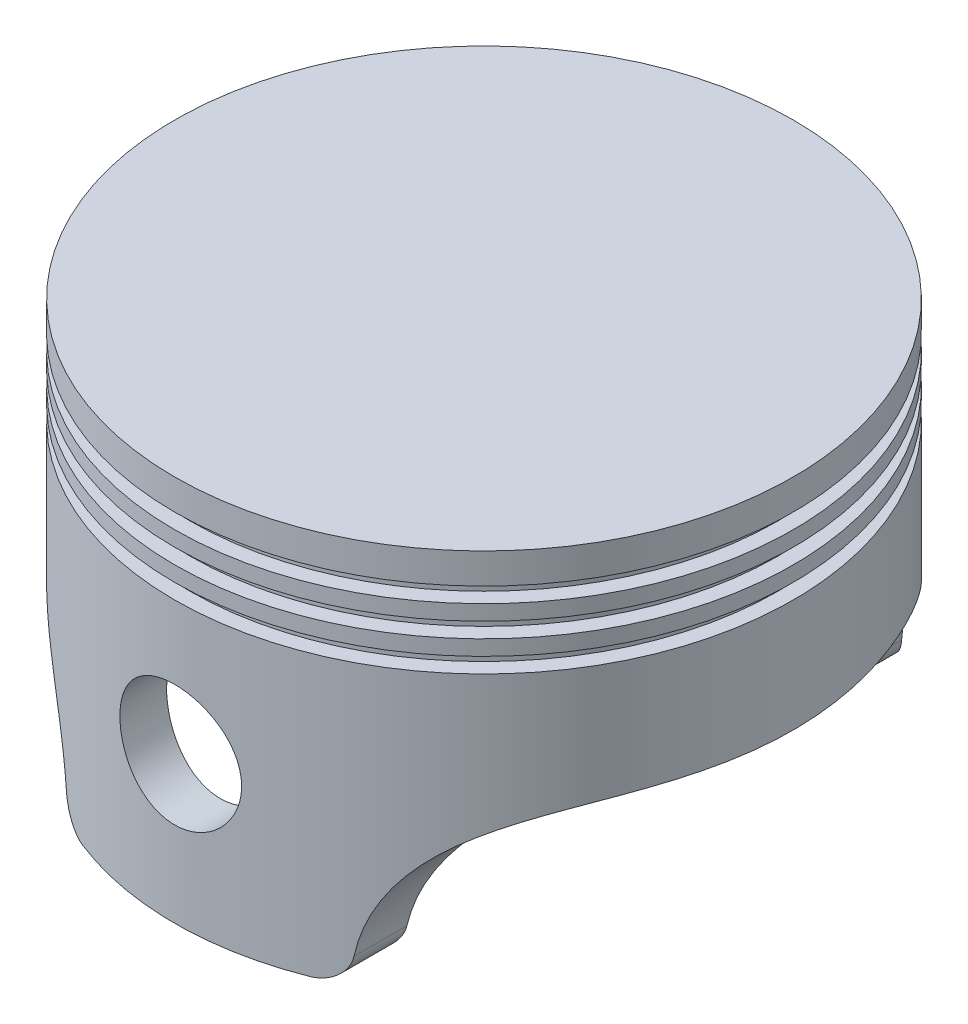
SolidWorks part; units mm, degrees
material "Plain Carbon Steel"
ref_plane "Front Plane" through (0, 0, 0) normal (0, 0, 1) x (1, 0, 0)
ref_plane "Top Plane" through (0, 0, 0) normal (0, 1, 0) x (1, 0, 0)
ref_plane "Right Plane" through (0, 0, 0) normal (1, 0, 0) x (0, 0, -1)
sketch "Sketch2" plane through (0, 0, 0) normal (0, 1, 0) x (1, 0, 0)
  circle A0 centre (0, 0) radius 50.8
  dimension "D1" = 101.6
extrude "Boss-Extrude1" add sketch "Sketch2" along normal mid plane 63.5
shell "Shell1" thickness 7.5 removed face at (0, -31.75, 50.8)
sketch "Sketch4" plane through (0, 24.25, 0) normal (0, -1, 0) x (1, 0, 0)
  line L0 (-42.6455, 7.5) -> (42.6455, 7.5)
  line L2 (-41.4565, 12.5) -> (41.4565, 12.5)
  circle A2 centre (0, 0) radius 43.3 construction
  arc A4 (-42.6455, 7.5) -> (-41.4565, 12.5) centre (0, 0) cw
  arc A5 (41.4565, 12.5) -> (42.6455, 7.5) centre (0, 0) cw
  circle A6 centre (0, 0) radius 43.3 construction
  dimension "D1" = 5
  dimension "D2" = 7.5
extrude "Boss-Extrude5" add sketch "Sketch4" along normal blind 28.5 contours A5 L0 A4 L2
mirror "Mirror1" about plane through (0, 0, 0) normal (0, 0, 1) of "Boss-Extrude5"
sketch "Sketch6" plane through (0, 0, 0) normal (0, 0, 1) x (1, 0, 0)
  line L0 (0, 0) -> (0, 58.5754) construction
  line L15 (-50.8, -31.75) -> (50.8, -31.75) construction
  line L16 (0, -7.75) -> (0, -31.75) construction
  line L17 (50.8, -31.75) -> (50.8, -4.25)
  line L18 (50.8, -31.75) -> (50.8, 31.75) construction
  line L20 (50.8, -31.75) -> (23.3, -31.75)
  circle A1 centre (0, -7.75) radius 10
  arc A2 (23.3, -31.75) -> (50.8, -4.25) centre (50.8, -31.75) cw
  dimension "D7" = 24
  dimension "D6" = 20
  dimension "D8" = 27.5
extrude "Cut-Extrude2" cut sketch "Sketch6" against normal through all both and the other way through all
mirror "Mirror2" about plane through (0, 0, 0) normal (1, 0, 0) of "Cut-Extrude2"
sketch "Sketch8" plane through (0, 0, 0) normal (0, 0, 1) x (1, 0, 0)
  line L0 (-50.8, 31.75) -> (-50.8, -4.25) construction
  line L1 (-50.8, 26.75) -> (-48.3, 26.75)
  line L2 (-50.8, 26.75) -> (-50.8, 24.25)
  line L3 (-50.8, 24.25) -> (-48.3, 24.25)
  line L4 (-48.3, 26.75) -> (-48.3, 24.25)
  line L5 (0, 0) -> (0, 53.44) construction
  line L6 (50.8, 31.75) -> (-50.8, 31.75) construction
  line L7 (-50.8, 21.75) -> (-48.3, 21.75)
  line L8 (-50.8, 21.75) -> (-50.8, 19.25)
  line L9 (-50.8, 19.25) -> (-48.3, 19.25)
  line L10 (-48.3, 21.75) -> (-48.3, 19.25)
  line L11 (-50.8, 16.75) -> (-48.3, 16.75)
  line L12 (-50.8, 16.75) -> (-50.8, 14.25)
  line L13 (-50.8, 14.25) -> (-48.3, 14.25)
  line L14 (-48.3, 16.75) -> (-48.3, 14.25)
  line L15 (-23.3, -31.75) -> (23.3, -31.75) construction
  dimension "D1" = 5
  dimension "D2" = 2.5
  dimension "D3" = 2.5
  dimension "D5" = 46
  dimension "D4" = 3
revolve "Cut-Revolve3" cut sketch "Sketch8" angle 360 about L5
fillet "Fillet1" radius 2 4 edges at (0, 24.25, -43.3) (0, 24.25, 43.3) (-43.3, 24.25, 0) (43.3, 24.25, 0) tangent propagation no
fillet "Fillet2" radius 5 4 edges at (-23.3, -31.75, -40.819) (23.3, -31.75, -40.819) (-23.3, -31.75, 40.819) (23.3, -31.75, 40.819)
